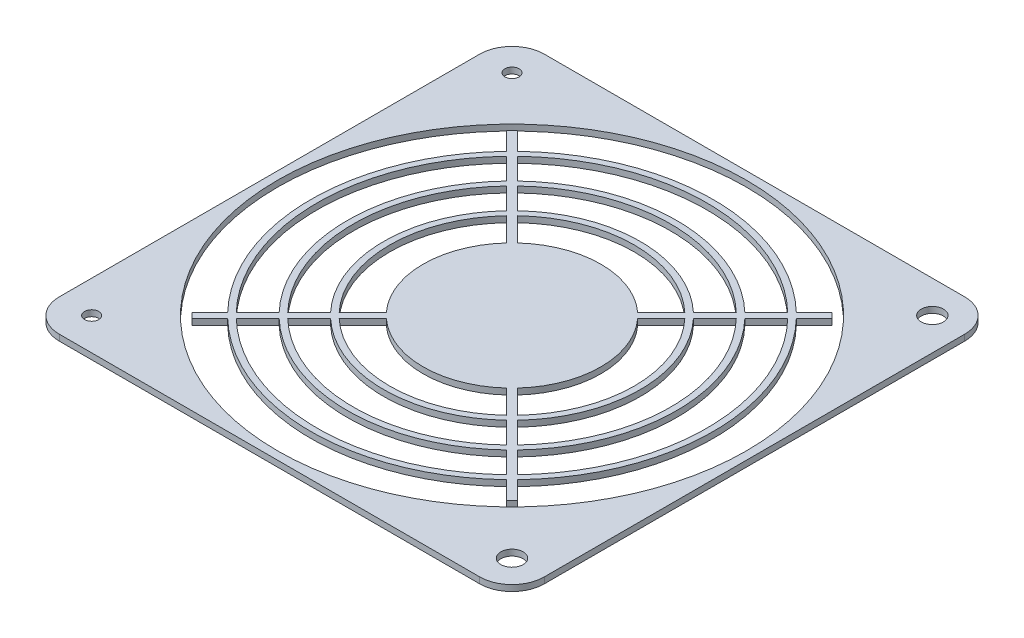
SolidWorks part; units mm, degrees
ref_plane "前视基准面" through (0, 0, 0) normal (0, 0, 1) x (1, 0, 0)
ref_plane "上视基准面" through (0, 0, 0) normal (0, 1, 0) x (1, 0, 0)
ref_plane "右视基准面" through (0, 0, 0) normal (1, 0, 0) x (0, 0, -1)
other "Configuration Table"
sketch "草图1" plane through (0, 0, 0) normal (0, 1, 0) x (1, 0, 0)
  line L0 (-52, 60) -> (52, 60)
  line L1 (60, 52) -> (60, -52)
  line L2 (52, -60) -> (-52, -60)
  line L3 (-60, -52) -> (-60, 52)
  arc A0 (52, 60) -> (60, 52) centre (52, 52) cw
  arc A1 (60, -52) -> (52, -60) centre (52, -52) cw
  arc A2 (-52, -60) -> (-60, -52) centre (-52, -52) cw
  arc A3 (-60, 52) -> (-52, 60) centre (-52, 52) cw
  circle A4 centre (52, 52) radius 2.75
  circle A5 centre (52, -52) radius 2.75
  circle A6 centre (-52, 52) radius 1.75
  circle A7 centre (-52, -52) radius 1.75
  circle A8 centre (0, 0) radius 58
extrude "凸台-拉伸1" add sketch "草图1" along normal blind 1.5
sketch "草图2" plane through (0, 0, 0) normal (0, 1, 0) x (1, 0, 0)
  circle A0 centre (0, 0) radius 22
extrude "凸台-拉伸2" add sketch "草图2" along normal blind 1.5
sketch "草图3" plane through (0, 0, 0) normal (0, 1, 0) x (1, 0, 0)
  circle A0 centre (0, 0) radius 31.75
  circle A1 centre (0, 0) radius 30.25
extrude "凸台-拉伸3" add sketch "草图3" along normal blind 1.5
sketch "草图4" plane through (0, 0, 0) normal (0, 1, 0) x (1, 0, 0)
  circle A0 centre (0, 0) radius 40.75
  circle A1 centre (0, 0) radius 39.25
extrude "凸台-拉伸4" add sketch "草图4" along normal blind 1.5
sketch "草图5" plane through (0, 0, 0) normal (0, 1, 0) x (1, 0, 0)
  circle A0 centre (0, 0) radius 49.75
  circle A1 centre (0, 0) radius 48.25
extrude "凸台-拉伸5" add sketch "草图5" along normal blind 1.5
extrude "凸台-拉伸6" add sketch "草图5<2>" along normal blind 1.5
sketch "草图5<2>" plane through (0, 0, 0) normal (0, 1, 0) x (1, 0, 0) same geometry as "草图5"
extrude "凸台-拉伸7" add sketch "草图5<3>" along normal blind 1.5
sketch "草图5<3>" plane through (0, 0, 0) normal (0, 1, 0) x (1, 0, 0) same geometry as "草图5"
sketch "草图8" plane through (0, 0, 0) normal (0, 1, 0) x (1, 0, 0)
  line L0 (-38.9262, -40.2697) -> (40.2697, 38.9262)
  line L1 (40.2697, 38.9262) -> (38.9262, 40.2697)
  line L2 (38.9262, 40.2697) -> (-40.2697, -38.9262)
  line L3 (-40.2697, -38.9262) -> (-38.9262, -40.2697)
extrude "凸台-拉伸8" add sketch "草图8" along normal blind 1.5
sketch "草图9" plane through (0, 0, 0) normal (0, 1, 0) x (1, 0, 0)
  line L0 (40.2697, -38.9262) -> (-38.9262, 40.2697)
  line L1 (-38.9262, 40.2697) -> (-40.2697, 38.9262)
  line L2 (-40.2697, 38.9262) -> (38.9262, -40.2697)
  line L3 (38.9262, -40.2697) -> (40.2697, -38.9262)
extrude "凸台-拉伸9" add sketch "草图9" along normal blind 1.5
